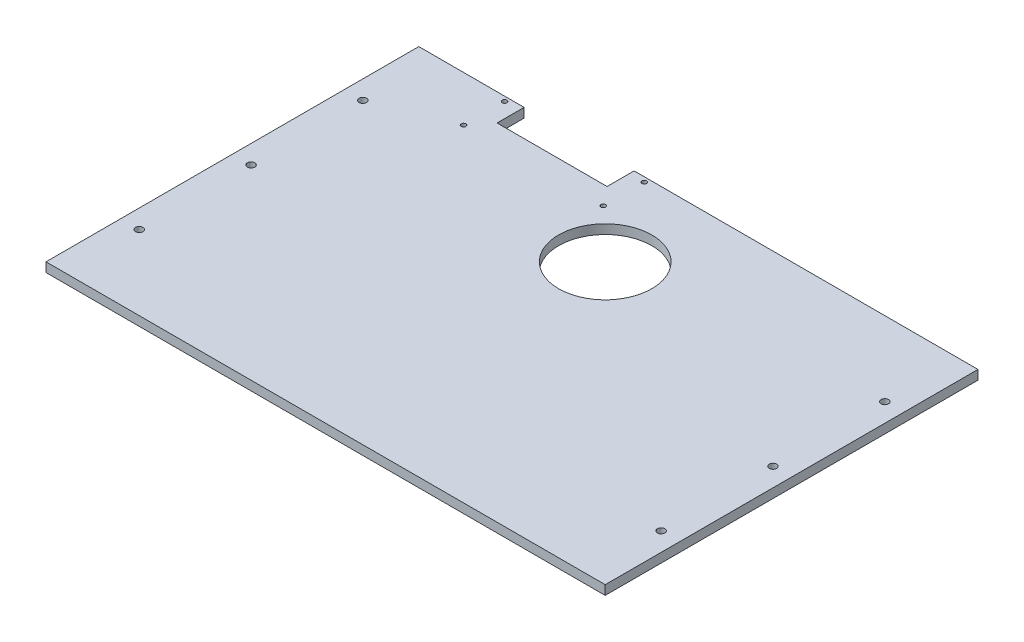
SolidWorks part; units mm, degrees
ref_plane "前视基准面" through (0, 0, 0) normal (0, 0, 1) x (1, 0, 0)
ref_plane "上视基准面" through (0, 0, 0) normal (0, 1, 0) x (1, 0, 0)
ref_plane "右视基准面" through (0, 0, 0) normal (1, 0, 0) x (0, 0, -1)
sketch "Sketch1" plane through (0, 0, 0) normal (0, 1, 0) x (1, 0, 0)
  line L1 (-150, 100) -> (150, 100)
  line L2 (-150, 100) -> (-150, -100)
  line L3 (-150, -100) -> (150, -100)
  line L4 (150, 100) -> (150, -100)
  line L5 (-150, 100) -> (150, -100) construction
  line L6 (-150, -100) -> (150, 100) construction
  point P0 (0, 0)
  dimension "D1" = 200
  dimension "D2" = 300
extrude "Boss-Extrude1" add sketch "Sketch1" along normal blind 5
sketch "Sketch2" plane through (0, 5, 0) normal (0, 1, 0) x (1, 0, 0)
  line L0 (-140, 100) -> (-140, -100) construction
  line L1 (150, 100) -> (-150, 100) construction
  line L2 (-150, -100) -> (150, -100) construction
  line L3 (-150, -90) -> (150, -90) construction
  line L4 (-150, 100) -> (-150, -100) construction
  line L5 (150, -100) -> (150, 100) construction
  line L6 (0, 0) -> (0, 100) construction
  line L7 (0, 0) -> (150, 0) construction
  line L8 (140, 100) -> (140, -100) construction
  circle A0 centre (-140, 0) radius 2
  circle A1 centre (-140, 60) radius 2
  circle A5 centre (-140, -60) radius 2
  circle A7 centre (140, -60) radius 2
  circle A8 centre (140, 60) radius 2
  circle A9 centre (140, 0) radius 2
  circle A13 centre (0, 50) radius 25
  dimension "D3" = 4
  dimension "D4" = 4
  dimension "D5" = 50
  dimension "D8" = 60
  dimension "D1" = 10
  dimension "D2" = 10
extrude "Cut-Extrude2" cut sketch "Sketch2" against normal through all
sketch "Sketch4" plane through (0, 5, 0) normal (0, 1, 0) x (1, 0, 0)
  line L0 (150, 100) -> (-150, 100) construction
  line L1 (-26.5, 97.5) -> (-101.5, 97.5) construction
  line L2 (-26.5, 97.5) -> (-26.5, 75.5) construction
  line L3 (-26.5, 75.5) -> (-101.5, 75.5) construction
  line L4 (-101.5, 97.5) -> (-101.5, 75.5) construction
  line L5 (-26.5, 97.5) -> (-101.5, 75.5) construction
  line L6 (-26.5, 75.5) -> (-101.5, 97.5) construction
  line L7 (-150, 100) -> (-150, -100) construction
  circle A0 centre (-101.5, 97.5) radius 1.25
  circle A1 centre (-26.5, 97.5) radius 1.25
  circle A2 centre (-26.5, 75.5) radius 1.25
  circle A3 centre (-101.5, 75.5) radius 1.25
  point P0 (-64, 86.5)
  dimension "D3" = 2.5
  dimension "D1" = 75
  dimension "D2" = 22
  dimension "D4" = 2.5
  dimension "D5" = 48.5
extrude "Cut-Extrude3" cut sketch "Sketch4" against normal through all
sketch "Sketch6" plane through (0, 0, 0) normal (0, -1, 0) x (1, 0, 0)
  line L0 (150, -100) -> (-150, -100) construction
  line L1 (-93.5, -100) -> (-34.5, -100)
  line L2 (-93.5, -100) -> (-93.5, -85.5)
  line L3 (-93.5, -85.5) -> (-34.5, -85.5)
  line L4 (-34.5, -100) -> (-34.5, -85.5)
  circle A0 centre (-101.5, -75.5) radius 1.25 construction
  circle A1 centre (-26.5, -75.5) radius 1.25 construction
  dimension "D1" = 8
  dimension "D2" = 8
  dimension "D3" = 10
extrude "Cut-Extrude4" cut sketch "Sketch6" against normal blind 5
